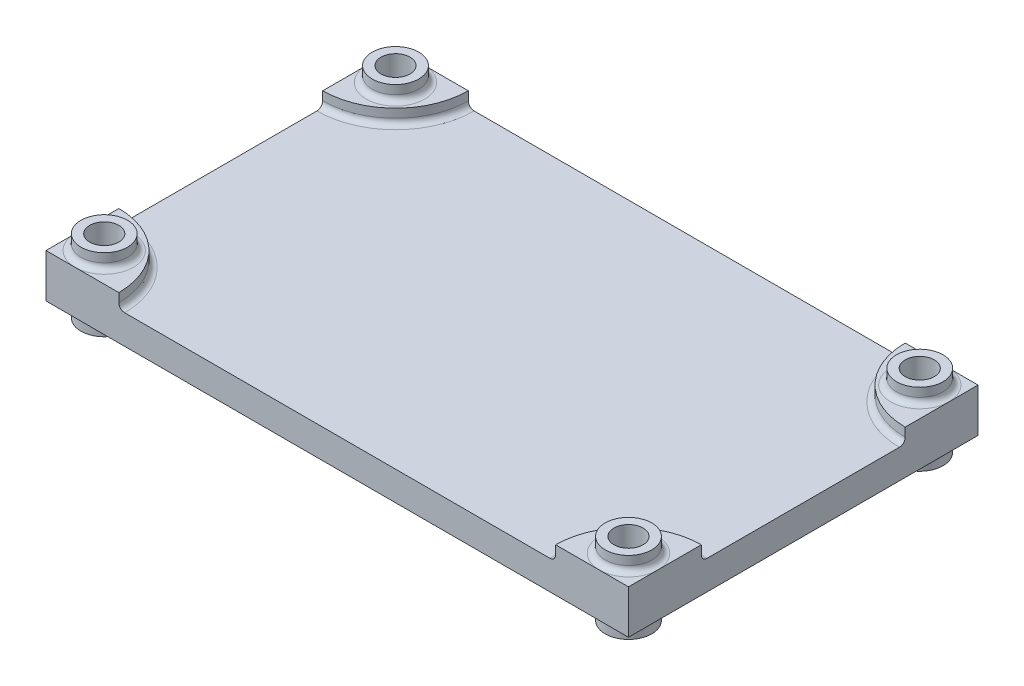
SolidWorks part; units mm, degrees
ref_plane "Front Plane" through (0, 0, 0) normal (0, 0, 1) x (1, 0, 0)
ref_plane "Top Plane" through (0, 0, 0) normal (0, 1, 0) x (1, 0, 0)
ref_plane "Right Plane" through (0, 0, 0) normal (1, 0, 0) x (0, 0, -1)
sketch "Sketch1" plane through (0, 0, 0) normal (0, 1, 0) x (1, 0, 0)
  line L1 (100, -60) -> (-100, -60)
  line L2 (100, -60) -> (100, 60)
  line L3 (100, 60) -> (-100, 60)
  line L4 (-100, -60) -> (-100, 60)
  line L5 (100, -60) -> (-100, 60) construction
  line L6 (100, 60) -> (-100, -60) construction
  point P0 (0, 0)
  dimension "D1" = 200
  dimension "D2" = 120
extrude "Boss-Extrude3" add sketch "Sketch1" along normal mid plane 5
sketch "Sketch3" plane through (0, 2.5, 0) normal (0, 1, 0) x (1, 0, 0)
  line L0 (-100, 60) -> (-80, 40) construction
  line L7 (80, 40) -> (100, 60) construction
  line L8 (-80, -40) -> (-100, -60) construction
  line L12 (80, -40) -> (100, -60) construction
  line L13 (-100, 60) -> (100, 60)
  line L16 (-100, 60) -> (-100, -60)
  line L17 (-100, -60) -> (100, -60)
  line L18 (100, 60) -> (100, -60)
  line L19 (0, -2.75) -> (0, 2.75) construction
  line L20 (-2.75, 0) -> (2.75, 0) construction
  circle A0 centre (-90, 50) radius 5
  circle A2 centre (90, -50) radius 5
  circle A4 centre (90, 50) radius 5
  circle A5 centre (-90, -50) radius 5
  arc A6 (-75, 60) -> (-100, 35) centre (-100, 60) cw
  arc A7 (75, 60) -> (100, 35) centre (100, 60) ccw
  arc A8 (75, -60) -> (100, -35) centre (100, -60) cw
  arc A9 (-75, -60) -> (-100, -35) centre (-100, -60) ccw
  point P0 (0, 0)
  line M5 (-100, 60) -> (-100, -60)
  line M6 (-100, -60) -> (100, -60)
  line M7 (100, -60) -> (100, 60)
  line M8 (100, 60) -> (-100, 60)
  dimension "D3" = 10
  dimension "D4" = 10
  dimension "D5" = 10
  dimension "D6" = 10
  dimension "D7" = 25
  dimension "D1" = 160
  dimension "D2" = 80
extrude "Boss-Extrude4" add sketch "Sketch3" along normal blind 5 contours A6 L13 A0 M5 | A7 L18 A4 M8 | A8 L17 A2 M7 | A9 A5 M6 M5 region at (-87.5, 2.5, -59.6464) region at (87.5, 2.5, -59.6464) region at (-82.5723, 2.5, 42.5723) region at (99.6464, 2.5, 47.5)
sketch "Sketch4" plane through (0, 7.5, 0) normal (0, 1, 0) x (1, 0, 0)
  line L0 (0, -5.5) -> (0, 5.5) construction
  line L1 (-5.5, 0) -> (5.5, 0) construction
  circle A0 centre (-90, 50) radius 8
  circle A1 centre (90, 50) radius 8
  circle A2 centre (-90, 50) radius 5
  circle A3 centre (90, 50) radius 5
  circle A4 centre (-90, -50) radius 5
  circle A5 centre (90, -50) radius 8
  circle A6 centre (-90, -50) radius 8
  circle A7 centre (90, -50) radius 5
extrude "Boss-Extrude5" add sketch "Sketch4" along normal blind 5
fillet "Fillet1" radius 2 8 edges at (82.3223, 2.5, 42.3223) (90, 7.5, 58) (90, 7.5, -58) (82.3223, 2.5, -42.3223) (-82.3223, 2.5, -42.3223) (-90, 7.5, -42) (-82.3223, 2.5, 42.3223) (-90, 7.5, 42)
mirror "Mirror2" about plane through (0, 0, 0) normal (0, 1, 0) of "Boss-Extrude4", "Boss-Extrude5"
fillet "Fillet2" radius 2 4 edges at (90, -7.5, -58) (-90, -7.5, -58) (90, -7.5, 42) (-90, -7.5, 42)
sketch "Sketch7" plane through (0, -2.5, 0) normal (0, -1, 0) x (1, 0, 0)
  line L0 (-75, 60) -> (75, 60)
  line L1 (-75.0801, 58) -> (75, 58)
  line L2 (-75, 58) -> (75, 58) construction
  line L3 (13.75, 0) -> (-13.75, 0) construction
  line L4 (0, -13.75) -> (0, 13.75) construction
  line L5 (75, 58) -> (75.0801, 58)
  line L6 (100, 35) -> (100, -35) construction
  line L7 (100, 50) -> (100, 35) construction
  line L8 (98, 35.0801) -> (98, -35.0801)
  line L9 (100, -35) -> (100, 35)
  line L10 (-75, -60) -> (-90, -60) construction
  line L11 (90, -60) -> (75, -60) construction
  line L12 (-100, -50) -> (-100, -35) construction
  line L13 (-100, 35) -> (-100, 50) construction
  line L14 (-98, -35.0801) -> (-98, 35.0801)
  line L15 (-100, 60) -> (100, 60)
  line L16 (-100, 60) -> (-100, -60)
  line L17 (-100, -60) -> (100, -60)
  line L18 (100, 60) -> (100, -60)
  line L19 (-75.0801, -58) -> (75.0801, -58)
  arc A0 (75, 60) -> (100, 35) centre (100, 60) ccw construction
  arc A1 (-75, 60) -> (-101.4921, 35.0446) centre (-100, 60) cw
  arc A2 (-100, 35) -> (-75, 60) centre (-100, 60) ccw construction
  arc A3 (-75, -60) -> (-101.4921, -35.0446) centre (-100, -60) ccw
  arc A4 (75, -60) -> (101.4921, -35.0446) centre (100, -60) cw
  arc A5 (75, 60) -> (101.4921, 35.0446) centre (100, 60) ccw
  point P9 (75.0801, 58)
  point P29 (75.0801, 58)
  point P30 (75.0801, 58)
  point P31 (98, 35.0801)
  point P32 (98, -35.0801)
  point P34 (75.0801, 58)
  point P45 (-98, 35.0801)
  point P46 (-98, -35.0801)
  point P47 (75.0801, -58)
  point P48 (-75.0801, -58)
  line M3 (75, 60) -> (-75, 60)
  arc M4 (-75, 60) -> (-100, 35) centre (-100, 60) cw
  line M5 (-100, 35) -> (-100, -35)
  arc M6 (-100, -35) -> (-75, -60) centre (-100, -60) cw
  line M7 (-75, -60) -> (75, -60)
  arc M8 (75, -60) -> (100, -35) centre (100, -60) cw
  line M9 (100, -35) -> (100, 35)
  arc M10 (100, 35) -> (75, 60) centre (100, 60) cw
  dimension "D2" = 2
  dimension "D3" = 2
  dimension "D4" = 2
  dimension "D5" = 2
  dimension "D6" = 2
  dimension "D7" = 2
  dimension "D1" = 2
extrude "Boss-Extrude6" add sketch "Sketch7" along normal blind 5 contours L14 M6 M4 M5 | L1 L5 M10 M3 M4 | L8 M10 M8 M9 | L19 M6 M7 M8 region at (0, -2.5, 58.9998) region at (-98.9996, -2.5, 0) region at (98.9996, -2.5, 0) region at (0, -2.5, -58.9998)
